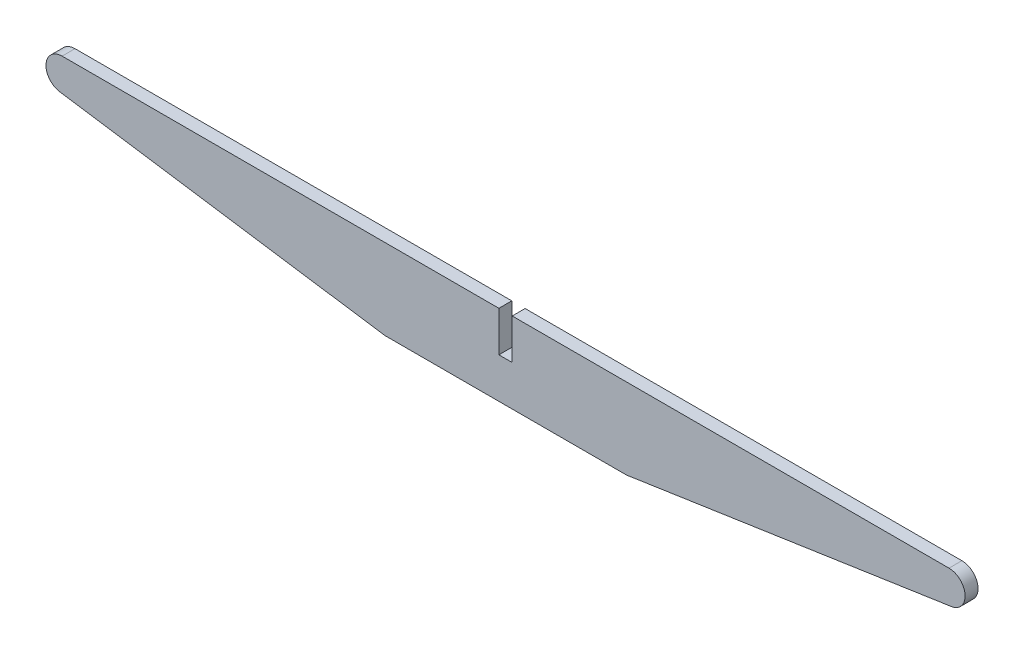
SolidWorks part; units mm, degrees
ref_plane "Front Plane" through (0, 0, 0) normal (0, 0, 1) x (1, 0, 0)
ref_plane "Top Plane" through (0, 0, 0) normal (0, 1, 0) x (1, 0, 0)
ref_plane "Right Plane" through (0, 0, 0) normal (1, 0, 0) x (0, 0, -1)
sketch "Sketch1" plane through (0, 0, 0) normal (0, 0, 1) x (1, 0, 0)
  line L0 (-110, 0) -> (110, 0)
  line L9 (110.5912, -7.9561) -> (30, -20)
  line L11 (-30, -20) -> (0, -20)
  line L12 (30, -20) -> (0, -20)
  line L16 (0, 0) -> (0, -20) construction
  line L18 (-110.5912, -7.9561) -> (-30, -20)
  arc A0 (110, 0) -> (110.5912, -7.9561) centre (110, -4) cw
  arc A1 (-110, 0) -> (-110.5912, -7.9561) centre (-110, -4) ccw
  point P0 (100, 0)
  dimension "D2" = 10
  dimension "D3" = 4
  dimension "D4" = 60
  dimension "D9" = 200
  dimension "D10" = 20
extrude "Boss-Extrude1" add sketch "Sketch1" along normal mid plane 3.2
sketch "Sketch2" plane through (0, 0, 1.6) normal (0, 0, 1) x (1, 0, 0)
  line L0 (-30, -20) -> (30, -20) construction
  line L1 (-1.65, -20) -> (1.65, -20)
  line L2 (-1.65, -20) -> (-1.65, -10)
  line L3 (-1.65, -10) -> (1.65, -10)
  line L4 (1.65, -20) -> (1.65, -10)
  line L5 (110, 0) -> (-110, 0) construction
  line L6 (-1.65, 0) -> (1.65, 0)
  line L7 (-1.65, 0) -> (-1.65, -10)
  line L8 (-1.65, -10) -> (1.65, -10)
  line L9 (1.65, 0) -> (1.65, -10)
  point P10 (0, 0)
  line M2 (110, 0) -> (-110, 0)
  line M13 (-30, -20) -> (30, -20)
  dimension "D1" = 3.3
extrude "lower main slot" [suppressed] cut sketch "Sketch2" against normal up to next contours L4 L3 L2 M13
extrude "Cut-Extrude2" cut sketch "Sketch2<4>" against normal up to next contours L9 L7 L3 M2 region at (0, -5, 1.6)
sketch "Sketch2<4>" plane through (0, 0, 1.6) normal (0, 0, 1) x (1, 0, 0) same geometry as "Sketch2"
